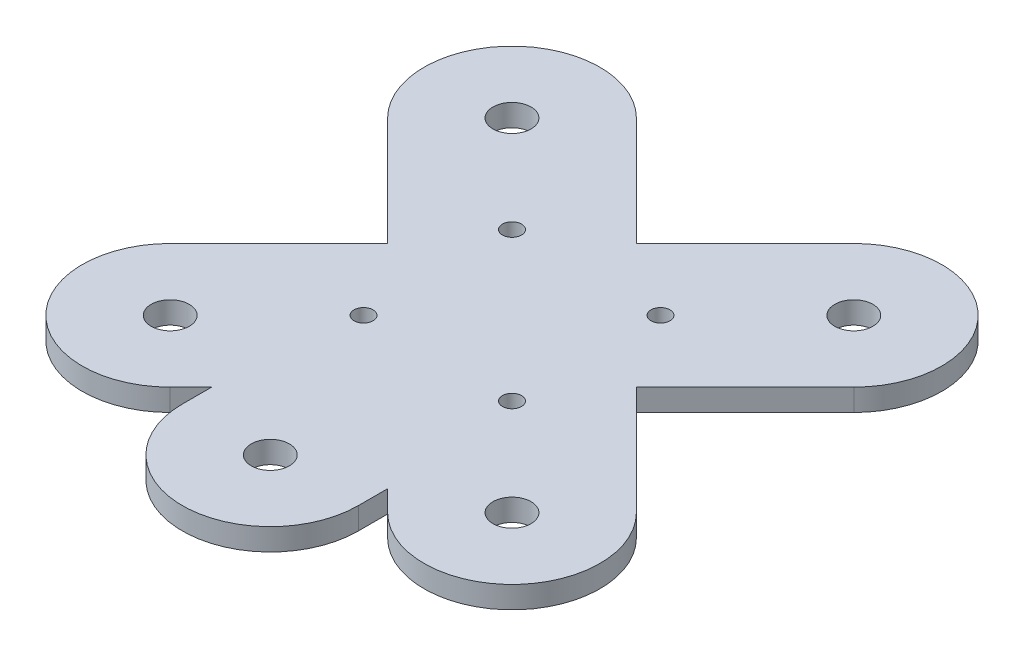
SolidWorks part; units mm, degrees
ref_plane "Front" through (0, 0, 0) normal (0, 0, 1) x (1, 0, 0)
ref_plane "Top" through (0, 0, 0) normal (0, 1, 0) x (1, 0, 0)
ref_plane "Right" through (0, 0, 0) normal (1, 0, 0) x (0, 0, -1)
sketch "Esquisse2" plane through (0, 0, 0) normal (0, 1, 0) x (1, 0, 0)
  line L0 (-30, 30) -> (30, -30) construction
  line L1 (30, 30) -> (30, -30) construction
  line L2 (30, -30) -> (-30, -30) construction
  line L3 (-30, -30) -> (-30, 30) construction
  line L4 (-30, 30) -> (30, 30) construction
  line L5 (30, 30) -> (-30, -30) construction
  line L6 (-1.7157, 1.7157) -> (-58.2843, 58.2843) construction
  line L7 (-22.9289, -19.4975) -> (-79.4975, 37.0711)
  line L8 (19.4975, 22.9289) -> (-37.0711, 79.4975)
  line L11 (5, 11.5685) -> (5, 91.5685) construction
  line L15 (1.7157, 1.7157) -> (58.2843, 58.2843) construction
  line L16 (-19.4975, 22.9289) -> (37.0711, 79.4975)
  line L17 (21.5685, -5) -> (101.5685, -5) construction
  line L20 (22.9289, -19.4975) -> (79.4975, 37.0711)
  line L28 (1.7157, -1.7157) -> (58.2843, -58.2843) construction
  line L29 (-11.5685, -5) -> (-91.5685, -5) construction
  line L30 (22.9289, 19.4975) -> (79.4975, -37.0711)
  line L31 (-19.4975, -22.9289) -> (37.0711, -79.4975)
  line L32 (0, -2.4264) -> (0, -82.4264) construction
  line L33 (30, -2.4264) -> (30, -82.4264)
  line L34 (-30, -2.4264) -> (-30, -82.4264)
  line L35 (-1.7157, -1.7157) -> (-58.2843, -58.2843) construction
  line L36 (19.4975, -22.9289) -> (-37.0711, -79.4975)
  line L37 (-22.9289, 19.4975) -> (-79.4975, -37.0711)
  line L59 (0, 2.4264) -> (0, 82.4264) construction
  line L60 (-30, 2.4264) -> (-30, 82.4264)
  line L61 (30, 2.4264) -> (30, 82.4264)
  line L62 (2.4264, 0) -> (82.4264, 0) construction
  line L63 (2.4264, 30) -> (82.4264, 30)
  line L64 (2.4264, -30) -> (82.4264, -30)
  line L65 (-2.4264, 0) -> (-82.4264, 0) construction
  line L66 (-2.4264, -30) -> (-82.4264, -30)
  line L67 (-2.4264, 30) -> (-82.4264, 30)
  line L68 (0, 2.4264) -> (0, 82.4264) construction
  line L69 (-30, 2.4264) -> (-30, 82.4264)
  line L70 (30, 2.4264) -> (30, 82.4264)
  line L71 (2.4264, 0) -> (82.4264, 0) construction
  line L72 (2.4264, 30) -> (82.4264, 30)
  line L73 (2.4264, -30) -> (82.4264, -30)
  line L74 (-2.4264, 0) -> (-82.4264, 0) construction
  line L75 (-2.4264, -30) -> (-82.4264, -30)
  line L76 (-2.4264, 30) -> (-82.4264, 30)
  arc A0 (-22.9289, -19.4975) -> (19.4975, 22.9289) centre (-1.7157, 1.7157) ccw
  arc A1 (-37.0711, 79.4975) -> (-79.4975, 37.0711) centre (-58.2843, 58.2843) ccw
  arc A6 (-19.4975, 22.9289) -> (22.9289, -19.4975) centre (1.7157, 1.7157) ccw
  arc A7 (79.4975, 37.0711) -> (37.0711, 79.4975) centre (58.2843, 58.2843) ccw
  arc A16 (22.9289, 19.4975) -> (-19.4975, -22.9289) centre (1.7157, -1.7157) ccw
  arc A17 (37.0711, -79.4975) -> (79.4975, -37.0711) centre (58.2843, -58.2843) ccw
  arc A18 (30, -2.4264) -> (-30, -2.4264) centre (0, -2.4264) ccw
  arc A19 (-30, -82.4264) -> (30, -82.4264) centre (0, -82.4264) ccw
  arc A20 (19.4975, -22.9289) -> (-22.9289, 19.4975) centre (-1.7157, -1.7157) ccw
  arc A21 (-79.4975, -37.0711) -> (-37.0711, -79.4975) centre (-58.2843, -58.2843) ccw
  arc A42 (-30, 2.4264) -> (30, 2.4264) centre (0, 2.4264) ccw
  arc A43 (30, 82.4264) -> (-30, 82.4264) centre (0, 82.4264) ccw
  arc A44 (2.4264, 30) -> (2.4264, -30) centre (2.4264, 0) ccw
  arc A45 (82.4264, -30) -> (82.4264, 30) centre (82.4264, 0) ccw
  arc A46 (-2.4264, -30) -> (-2.4264, 30) centre (-2.4264, 0) ccw
  arc A47 (-82.4264, 30) -> (-82.4264, -30) centre (-82.4264, 0) ccw
  point P0 (0, 0)
  point P9 (-30, 30)
  point P19 (5, 51.5685)
  point P22 (0, 49.4975)
  point P29 (30, 30)
  point P33 (61.5685, -5)
  point P39 (49.4975, 0)
  point P46 (30, -30)
  point P53 (0, -42.4264)
  point P61 (-51.5685, -5)
  point P63 (-30, -30)
  point P66 (5, -5)
  point P71 (-49.4975, 0)
  point P76 (0, 0)
  point P109 (0, 49.4975)
  point P116 (49.4975, 0)
  point P123 (-49.4975, 0)
  point P130 (0, 42.4264)
  point P137 (42.4264, 0)
  point P144 (-42.4264, 0)
  point P151 (0, 42.4264)
  point P158 (42.4264, 0)
  point P165 (-42.4264, 0)
  point P172 (0, 42.4264)
  point P179 (42.4264, 0)
  point P186 (-42.4264, 0)
  dimension "D4" = 30
  dimension "D1" = 60
  dimension "D2" = 60
  dimension "D3" = 80
  dimension "D5" = 8
extrude "Boss.-Extru.1" add sketch "Esquisse2" along normal blind 7.5 contours A17 | L36 A21 L37 A20 | L33 A19 L34 A18 | L30 A17 L31 A16 | L8 A1 L7 A0 | L16 A7 L20 A6
sketch "Esquisse4" plane through (0, 0, 0) normal (0, -1, 0) x (-1, 0, 0)
  line L0 (0, 0) -> (-79.4975, -79.4975) construction
  line L1 (-25.317, -46.5302) -> (-7.6393, -28.8525)
  line L2 (-7.6393, -28.8525) -> (-28.8525, -7.6393)
  line L3 (-28.8525, -7.6393) -> (-46.5302, -25.317)
  line L4 (-42.4264, 0) -> (-79.4975, -37.0711) construction
  line L5 (-46.5302, 25.317) -> (-28.8525, 7.6393)
  line L6 (-7.6393, 28.8525) -> (-25.317, 46.5302)
  line L7 (-28.8525, 7.6393) -> (-7.6393, 28.8525)
  line L8 (25.317, 46.5302) -> (7.6393, 28.8525)
  line L9 (28.8525, 7.6393) -> (46.5302, 25.317)
  line L10 (7.6393, 28.8525) -> (28.8525, 7.6393)
  line L11 (46.5302, -25.317) -> (28.8525, -7.6393)
  line L12 (7.6393, -28.8525) -> (25.317, -46.5302)
  line L13 (28.8525, -7.6393) -> (7.6393, -28.8525)
  arc A0 (-79.4975, -37.0711) -> (-37.0711, -79.4975) centre (-58.2843, -58.2843) ccw construction
  arc A1 (-25.317, -46.5302) -> (-46.5302, -25.317) centre (-58.2843, -58.2843) ccw
  arc A2 (-46.5302, 25.317) -> (-25.317, 46.5302) centre (-58.2843, 58.2843) ccw
  arc A3 (25.317, 46.5302) -> (46.5302, 25.317) centre (58.2843, 58.2843) ccw
  arc A4 (46.5302, -25.317) -> (25.317, -46.5302) centre (58.2843, -58.2843) ccw
  point P36 (0, 0)
  dimension "D5" = 35
  dimension "D1" = 25
  dimension "D2" = 25
  dimension "D3" = 15
  dimension "D4" = 30
extrude "Enlèv. mat.-Extru.1" cut sketch "Esquisse4" against normal blind 2 contours L0 L2 L3 A1 | L2 L0 A1 L1 | A2 L5 L7 L6 | A3 L8 L10 L9 | A4 L11 L13 L12 region at (20.863, 0, 31.7295) region at (31.7295, 0, 20.863) region at (26.2963, 0, -26.2963) region at (-26.2963, 0, -26.2963) region at (-26.2963, 0, 26.2963)
sketch "Esquisse5" plane through (0, 2, 0) normal (0, -1, 0) x (-1, 0, 0)
  line L0 (0, 0) -> (-58.2843, -58.2843) construction
  line L1 (-58.2843, -58.2843) -> (0, 0) construction
  line L2 (-7.6393, -28.8525) -> (-28.8525, -7.6393) construction
  circle A0 centre (-25.317, -25.317) radius 3.25
  circle A1 centre (-25.317, 25.317) radius 3.25
  circle A2 centre (25.317, 25.317) radius 3.25
  circle A3 centre (25.317, -25.317) radius 3.25
  point P17 (0, 0)
  dimension "D1" = 6.5
  dimension "D2" = 10
extrude "Enlèv. mat.-Extru.2" cut sketch "Esquisse5" against normal through all
sketch "Esquisse7" plane through (0, 0, 0) normal (0, -1, 0) x (-1, 0, 0)
  circle A0 centre (0, -82.4264) radius 6.5
  circle A1 centre (-58.2843, -58.2843) radius 6.5
  circle A2 centre (-82.4264, 0) radius 6.5 [skipped]
  circle A3 centre (-58.2843, 58.2843) radius 6.5
  circle A4 centre (0, 82.4264) radius 6.5 [skipped]
  circle A5 centre (58.2843, 58.2843) radius 6.5
  circle A6 centre (82.4264, 0) radius 6.5 [skipped]
  circle A7 centre (58.2843, -58.2843) radius 6.5
  point P20 (0, 0)
  dimension "D1" = 13
extrude "Enlèv. mat.-Extru.3" cut sketch "Esquisse7" against normal through all
